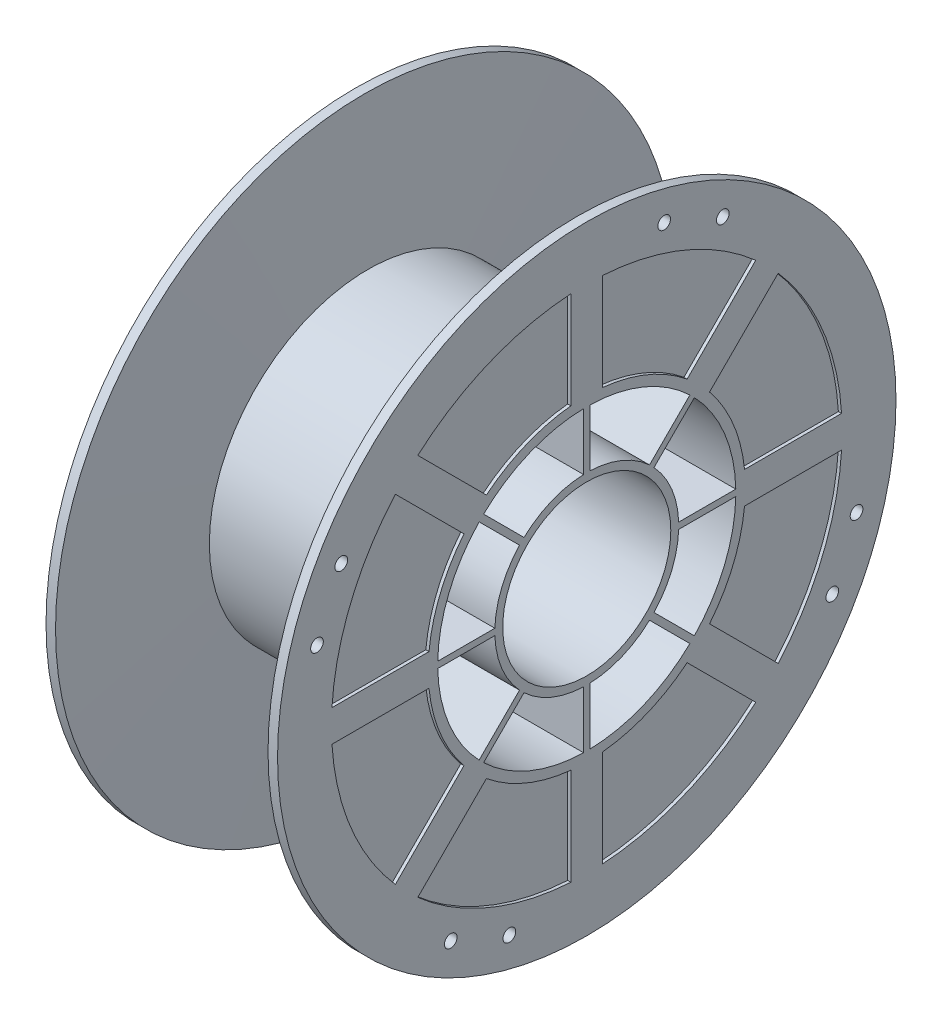
SolidWorks part; units mm, degrees
material "PS Medium/High Flow"
ref_plane "Front" through (0, 0, 0) normal (0, 0, 1) x (1, 0, 0)
ref_plane "Top" through (0, 0, 0) normal (0, 1, 0) x (1, 0, 0)
ref_plane "Right" through (0, 0, 0) normal (1, 0, 0) x (0, 0, -1)
sketch "Sketch1" plane through (0, 0, 0) normal (1, 0, 0) x (0, 0, -1)
  circle A0 centre (0, 0) radius 26.5
  circle A1 centre (0, 0) radius 50
  dimension "D1" = 53
  dimension "D2" = 100
extrude "Boss-Extrude1" add sketch "Sketch1" along normal blind 6
sketch "Sketch2" plane through (0, 0, 0) normal (1, 0, 0) x (0, 0, -1)
  line L0 (0, 29) -> (0, 47) construction
  line L1 (1, 46.9894) -> (1, 28.9828)
  line L2 (-1, 28.9828) -> (-1, 46.9894)
  circle A0 centre (0, 0) radius 26.5 construction
  circle A1 centre (0, 0) radius 26.5
  circle A2 centre (0, 0) radius 29
  circle A3 centre (0, 0) radius 50 construction
  circle A4 centre (0, 0) radius 50
  circle A5 centre (0, 0) radius 47
  dimension "D1" = 2.5
  dimension "D2" = 3
  dimension "D3" = 2
extrude "Boss-Extrude2" add sketch "Sketch2" along normal blind 36 and the other way blind 37 contours A4 A5 | A2 A1 region at (0, 19.5795, -20.2667) region at (0, 0, 48.5858)
extrude "Boss-Extrude3" add sketch "Sketch2<3>" along normal blind 36 and the other way blind 37 contours A2 L0 A5 L2 | L0 A2 L1 A5 region at (0, 37.9954, 0.5) region at (0, 37.9954, -0.5)
sketch "Sketch2<3>" plane through (0, 0, 0) normal (1, 0, 0) x (0, 0, -1) same geometry as "Sketch2"
pattern_circular "CirPattern1" count 8 over 360 about axis through (6, 0, 0) along (-1, 0, 0) of "Boss-Extrude3"
sketch "Sketch4" plane through (0, 0, 0) normal (0, 0, 1) x (1, 0, 0)
  line L0 (36, 80.5) -> (36, 97.5)
  line L1 (36, 97.5) -> (33, 97.5)
  line L2 (33, 97.5) -> (32, 50)
  line L3 (36, 50) -> (-37, 50) construction
  line L4 (32, 50) -> (35, 50)
  line L5 (0, 0) -> (86.16, 0) construction
  line L6 (36, 80.5) -> (35, 80.5)
  line L7 (35, 80.5) -> (35, 50)
  line L8 (36, 50) -> (36, 97.5) construction
  line L11 (-37, 50) -> (-37, 101.0975) construction
  line L12 (-33, 50) -> (-36, 50)
  line L13 (-37, 67.5) -> (-36, 67.5)
  line L14 (-37, 67.5) -> (-37, 97.5)
  line L15 (-37, 97.5) -> (-34, 97.5)
  line L16 (-34, 97.5) -> (-33, 50)
  line L17 (-36, 67.5) -> (-36, 50)
  dimension "D1" = 195
  dimension "D2" = 1
  dimension "D3" = 17
  dimension "D4" = 3
  dimension "D5" = 4
  dimension "D6" = 1
  dimension "D7" = 30
revolve "Revolve1" add sketch "Sketch4" angle 360 about L5
sketch "Sketch5" plane through (-36, 0, 0) normal (-1, 0, 0) x (0, 0, 1)
  line L0 (0, 0) -> (0, 73.5379) construction
  line L1 (5, 67.3146) -> (5, 49.7494)
  line L2 (-5, 67.3146) -> (-5, 49.7494)
  circle A0 centre (0, 0) radius 67.5 construction
  circle A1 centre (0, 0) radius 50 construction
  arc A2 (5, 67.3146) -> (-5, 67.3146) centre (0, 0) ccw
  circle A3 centre (0, 0) radius 50 construction
  arc A4 (5, 49.7494) -> (-5, 49.7494) centre (0, 0) ccw
  circle M1 centre (0, 0) radius 50
  circle M2 centre (0, 0) radius 67.5
  dimension "D1" = 10
extrude "Boss-Extrude4" add sketch "Sketch5" along normal blind 1 contours L0 A4 L1 M2 | L0 A2 L2 M1 region at (-36, 58.6773, -2.5015) region at (-36, 58.6773, 2.5015)
sketch "Sketch6" plane through (35, 0, 0) normal (1, 0, 0) x (0, 0, -1)
  line L0 (0, 0) -> (0, 97.5) construction
  line L1 (5, 80.3446) -> (5, 49.7494)
  line L2 (-5, 80.3446) -> (-5, 49.7494)
  circle A0 centre (0, 0) radius 97.5 construction
  circle A1 centre (0, 0) radius 80.5 construction
  circle A2 centre (0, 0) radius 50 construction
  arc A3 (5, 80.3446) -> (-5, 80.3446) centre (0, 0) ccw
  circle A4 centre (0, 0) radius 50 construction
  arc A5 (5, 49.7494) -> (-5, 49.7494) centre (0, 0) ccw
  dimension "D1" = 10
extrude "Boss-Extrude5" add sketch "Sketch6" along normal blind 1
pattern_circular "CirPattern2" count 8 over 360 about axis through (6, 0, 0) along (-1, 0, 0) of "Boss-Extrude5", "Boss-Extrude4"
sketch "Sketch7" plane through (36, 0, 0) normal (1, 0, 0) x (0, 0, -1)
  line L0 (0, 0) -> (37.3116, 90.0783) construction
  line L1 (5, 49.7494) -> (5, 80.3446) construction
  circle A0 centre (0, 0) radius 97.5 construction
  circle A1 centre (24.4118, 85.0665) radius 2
  circle A2 centre (42.8894, 77.4129) radius 2
  dimension "D2" = 4
  dimension "D1" = 22.5
  dimension "D3" = 20
  dimension "D4" = 88.5
extrude "Cut-Extrude1" cut sketch "Sketch7" against normal up to next
pattern_circular "CirPattern3" count 4 over 360 about axis through (6, 0, 0) along (-1, 0, 0) of "Cut-Extrude1"
ref_plane "Side plane 1" through (-35.5, 0, 0) normal (-1, 0, 0) x (0, 0, 1)
ref_plane "Side plane 2" through (34.5, 0, 0) normal (1, 0, 0) x (0, 0, -1)
sketch "Sketch8" plane through (-35.5, 0, 0) normal (-1, 0, 0) x (0, 0, 1)
  circle A0 centre (0, 0) radius 97.5 construction
  circle A1 centre (0, 0) radius 97.5 construction
sketch "Sketch9" plane through (34.5, 0, 0) normal (1, 0, 0) x (0, 0, -1)
  circle A0 centre (0, 0) radius 97.5 construction
  circle A1 centre (0, 0) radius 97.5 construction
